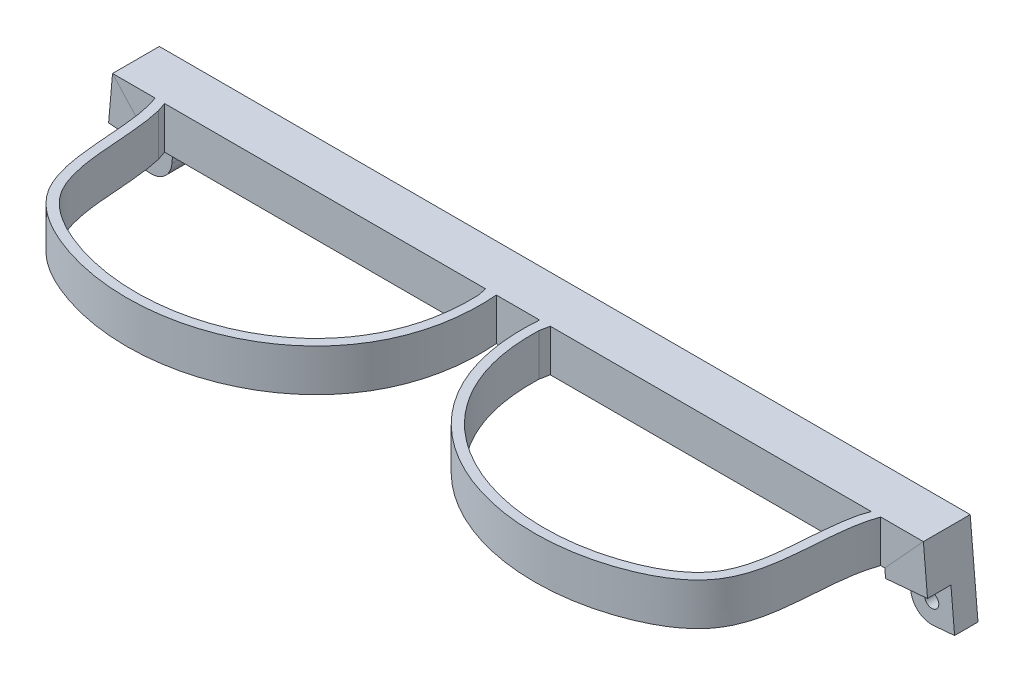
SolidWorks part; units mm, degrees
ref_plane "前视基准面" through (0, 0, 0) normal (0, 0, 1) x (1, 0, 0)
ref_plane "上视基准面" through (0, 0, 0) normal (0, 1, 0) x (1, 0, 0)
ref_plane "右视基准面" through (0, 0, 0) normal (1, 0, 0) x (0, 0, -1)
sketch "草图1" plane through (0, 0, 0) normal (0, 1, 0) x (1, 0, 0)
  line L0 (-85, 29.8187) -> (85, 29.8187)
  line L1 (85, 29.8187) -> (85, -30.1813)
  line L2 (85, -30.1813) -> (-85, -30.1813)
  line L3 (-85, -30.1813) -> (-85, 29.8187)
  line L4 (-77.5, 21.6616) -> (77.5, 21.6616)
  line L5 (-77.5, 21.6616) -> (-77.5, 11.6616)
  line L6 (-77.5, 11.6616) -> (-4.6224, 11.6616)
  line L8 (-74.8263, 9.6616) -> (-6.5113, 9.6616) construction
  line L10 (-4.6224, 11.6616) -> (4.6224, 11.6616)
  line L11 (0, 29.8187) -> (0, -30.1813) construction
  line L12 (77.5, 11.6616) -> (4.6224, 11.6616)
  line L13 (77.5, 21.6616) -> (77.5, 11.6616)
  spline S0 degree 3 poles (-77.5, 11.6616) (-74.4077, 3.1869) (-78.1308, -15.9273) (-40.2589, -37.426) (-2.1163, -20.689) (-4.6224, 11.6616) knots 0 0 0 0 0.246122 0.369792 1 1 1 1
  spline S1 degree 1 poles (-74.8263, 9.6616) (-6.5113, 9.6616) knots 0 0 1 1 construction
  spline S2 degree 3 poles (-74.8263, 9.6616) (-74.5371, 8.4402) (-74.1186, 5.9785) (-73.6218, 0.8691) (-73.2546, -5.557) (-72.241, -11.3706) (-70.6014, -15.2078) (-68.2701, -18.4305) (-63.7315, -21.7629) (-56.8543, -24.5334) (-49.7226, -26.1197) (-40.0582, -26.6566) (-30.6361, -24.878) (-22.3142, -20.9083) (-16.8289, -16.8747) (-12.2912, -11.8166) (-9.4499, -6.76) (-7.8343, -2.2025) (-6.9771, 1.4731) (-6.5812, 4.7599) (-6.4697, 7.5102) (-6.4856, 8.9503) (-6.5113, 9.6616) knots 0.022831 0.022831 0.022831 0.022831 0.052972 0.083113 0.143395 0.203676 0.233817 0.263958 0.324239 0.384521 0.444802 0.505084 0.625647 0.685929 0.74621 0.806492 0.866773 0.896914 0.927055 0.957196 0.972266 0.987337 0.987337 0.987337 0.987337
  spline S3 degree 1 poles (-74.8263, 9.6616) (-75.4985, 11.6616) knots 0 0 1 1
  spline S4 degree 1 poles (-6.5113, 9.6616) (-6.9074, 11.6616) knots 0 0 1 1
  spline S5 degree 1 poles (74.8263, 9.6616) (75.4985, 11.6616) knots 0 0 1 1
  spline S6 degree 1 poles (6.5113, 9.6616) (6.9074, 11.6616) knots 0 0 1 1
  spline S7 degree 3 poles (74.8263, 9.6616) (74.5371, 8.4402) (74.1186, 5.9785) (73.6218, 0.8691) (73.2546, -5.557) (72.241, -11.3706) (70.6014, -15.2078) (68.2701, -18.4305) (63.7315, -21.7629) (56.8543, -24.5334) (49.7226, -26.1197) (40.0582, -26.6566) (30.6361, -24.878) (22.3142, -20.9083) (16.8289, -16.8747) (12.2912, -11.8166) (9.4499, -6.76) (7.8343, -2.2025) (6.9771, 1.4731) (6.5812, 4.7599) (6.4697, 7.5102) (6.4856, 8.9503) (6.5113, 9.6616) knots 0.022831 0.022831 0.022831 0.022831 0.052972 0.083113 0.143395 0.203676 0.233817 0.263958 0.324239 0.384521 0.444802 0.505084 0.625647 0.685929 0.74621 0.806492 0.866773 0.896914 0.927055 0.957196 0.972266 0.987337 0.987337 0.987337 0.987337
  spline S8 degree 3 poles (77.5, 11.6616) (74.4077, 3.1869) (78.1308, -15.9273) (40.2589, -37.426) (2.1163, -20.689) (4.6224, 11.6616) knots 0 0 0 0 0.246122 0.369792 1 1 1 1
  point P3 (0, 29.8187)
  point P25 (0, 11.6616)
  point P31 (0, 21.6616)
  dimension "D1" = 60
  dimension "D2" = 170
  dimension "D3" = 10
  dimension "D4" = 77.5
  dimension "D5" = 2
extrude "frame_前端" add sketch "草图1" along normal blind 9 contours L13 L4 L5 L6 L10 L12 | S8 L12 S5 S7 S6 | S4 S2 S3 L6 S0 region at (0, 0, -16.6616) region at (-76.4992, 0, -10.8291) region at (42.3457, 0, 27.4934)
sketch "左镜腿扫描截面草图" plane through (77.5, 0, 0) normal (1, 0, 0) x (0, 0, -1)
  line L0 (11.6616, 9) -> (11.6616, 0)
  line L1 (11.6616, 9) -> (11.6616, 0) construction
  line L2 (11.6616, 0) -> (21.6616, 0)
  line L3 (21.6616, 0) -> (21.6616, 9)
  line L4 (21.6616, 9) -> (11.6616, 9)
  line L5 (11.6616, 9) -> (21.6616, 0) construction
  line L6 (11.6616, 0) -> (21.6616, 9) construction
  point P7 (16.6616, 4.5)
ref_plane "左侧镜腿轨迹基准面" through (0, 0, -16.6616) normal (0, 0, -1) x (-1, 0, 0)
sketch "左侧镜腿轨迹草图" plane through (0, 0, -16.6616) normal (0, 0, -1) x (-1, 0, 0)
  line L0 (-77.5, 4.5) -> (-82.5, 4.5)
  line L1 (-77.5, 0) -> (-77.5, 9) construction
  line L2 (-82.5, 4.5) -> (-83.8073, -10.4429)
  dimension "D1" = 5
  dimension "D2" = 15
  dimension "D3" = 95
sweep "左侧connection生成" add profiles "左镜腿扫描截面草图" path "左侧镜腿轨迹草图"
sketch "草图20" plane through (0, 0, -21.6616) normal (0, 0, -1) x (-1, 0, 0)
  line L8 (-79.3245, -10.8351) -> (-83.8073, -10.4429)
  line L9 (-79.3245, -10.8351) -> (-88.2902, -10.0507) construction
  line L10 (-78.3765, 0) -> (-79.3245, -10.8351) construction
  line L11 (-78.9323, -6.3522) -> (-79.3245, -10.8351)
  arc A1 (-83.8073, -10.4429) -> (-78.9323, -6.3522) centre (-83.4151, -5.96) ccw
  point P13 (-79.3245, -10.8351)
  dimension "D1" = 4.5
extrude "左侧connection圆角化" cut sketch "草图20" against normal through all
sketch "孔左" plane through (0, 0, -21.6616) normal (0, 0, -1) x (-1, 0, 0)
  line L4 (-78.9323, -6.3522) -> (-78.3765, 0)
  line L5 (-78.3765, 0) -> (-86.6235, 9)
  line L6 (-86.6235, 9) -> (-88.2902, -10.0507)
  line L7 (-88.2902, -10.0507) -> (-83.8073, -10.4429)
  line L8 (-78.9323, -6.3522) -> (-78.3765, 0)
  line L9 (-78.3765, 0) -> (-86.6235, 9)
  line L10 (-86.6235, 9) -> (-88.2902, -10.0507)
  line L11 (-88.2902, -10.0507) -> (-83.8073, -10.4429)
  arc A1 (-83.8073, -10.4429) -> (-78.9323, -6.3522) centre (-83.4151, -5.96) ccw
  circle A3 centre (-83.4151, -5.96) radius 1.5
  arc A4 (-83.8073, -10.4429) -> (-78.9323, -6.3522) centre (-83.4151, -5.96) ccw
  dimension "D2" = 3
  dimension "D1" = 0
ref_plane "右侧镜腿轨迹基准面" through (0, 0, -16.6616) normal (0, 0, -1) x (-1, 0, 0)
sketch "草图22" plane through (0, 0, -16.6616) normal (0, 0, -1) x (-1, 0, 0)
  line L0 (77.5, 4.5) -> (82.5, 4.5)
  line L1 (77.5, 9) -> (77.5, 0) construction
  line L2 (82.5, 4.5) -> (83.8073, -10.4429)
  dimension "D1" = 5
  dimension "D2" = 15
  dimension "D3" = 95
sketch "草图23" plane through (-77.5, 0, 0) normal (-1, 0, 0) x (0, 0, 1)
  line L2 (-21.6616, 0) -> (-11.6616, 0)
  line L3 (-11.6616, 0) -> (-11.6616, 9)
  line L6 (-21.6616, 9) -> (-21.6616, 0)
  line L7 (-21.6616, 0) -> (-21.6616, 9) construction
  line L8 (-21.6616, 9) -> (-11.6616, 9) construction
  line L9 (-21.6616, 9) -> (-11.6616, 9)
sweep "右侧connection生成" add profiles "草图23" path "草图22"
sketch "草图24" plane through (0, 0, -21.6616) normal (0, 0, -1) x (-1, 0, 0)
  line L2 (88.2902, -10.0507) -> (79.3245, -10.8351) construction
  line L3 (79.3245, -10.8351) -> (83.8073, -10.4429)
  line L4 (79.3245, -10.8351) -> (78.9323, -6.3522)
  line L5 (78.3765, 0) -> (79.3245, -10.8351) construction
  circle A1 centre (83.4151, -5.96) radius 1.5
  arc A2 (78.9323, -6.3522) -> (83.8073, -10.4429) centre (83.4151, -5.96) ccw
  point P11 (83.4151, -6.0699)
  dimension "D3" = 3
  dimension "D1" = 4.5
extrude "右侧孔and_connection圆角化" cut sketch "草图24" against normal through all
ref_plane "线槽口草图基准面" through (0, 0, 0) normal (1, 0, 0) x (0, 0, -1)
sketch "草图25" plane through (0, 0, 0) normal (1, 0, 0) x (0, 0, -1)
  line L6 (21.6616, 9) -> (21.6616, -10.0507) construction
  line L9 (11.6616, 9) -> (21.6616, 0) construction
  line L10 (11.6616, 0) -> (21.6616, 9) construction
  line L11 (13.6616, 0) -> (13.6616, 7.2)
  line L12 (13.6616, 7.2) -> (19.6616, 7.2)
  line L13 (19.6616, 7.2) -> (19.6616, 0)
  line L14 (13.6616, 0) -> (19.6616, 0)
  dimension "D1" = 2
  dimension "D2" = 2
extrude "挖槽右" cut sketch "草图25" against normal blind 77.5
extrude "挖槽左" cut sketch "草图25<2>" along normal blind 77.5
sketch "草图25<2>" plane through (0, 0, 0) normal (1, 0, 0) x (0, 0, -1) same geometry as "草图25"
sketch "草图26" plane through (0, 0, -21.6616) normal (0, 0, -1) x (-1, 0, 0)
  line L6 (-88.2902, -10.0507) -> (-87.5058, -1.085)
  line L7 (-86.6235, 9) -> (-88.2902, -10.0507) construction
  line L8 (-87.5058, -1.085) -> (-78.5401, -1.8694)
  line L9 (-78.9323, -6.3522) -> (-78.3765, 0) construction
  line L10 (-78.5401, -1.8694) -> (-78.9323, -6.3522)
  line L11 (-88.2902, -10.0507) -> (-83.8073, -10.4429)
  line L12 (-88.2902, -10.0507) -> (-83.8073, -10.4429) construction
  arc A1 (-83.8073, -10.4429) -> (-78.9323, -6.3522) centre (-83.4151, -5.96) ccw
  dimension "D2" = 4.5
  dimension "D1" = 9
  dimension "D3" = 4.5
extrude "挖孔左" cut sketch "孔左" against normal through all contours A3
ref_plane "基准面1" through (0, 0, -16.6616) normal (0, 0, -1) x (-1, 0, 0)
sketch "草图27" plane through (0, 0, -16.6616) normal (0, 0, -1) x (-1, 0, 0)
  line L0 (-87.5058, -1.085) -> (-78.5401, -1.8694)
  line L1 (-78.5401, -1.8694) -> (-78.9323, -6.3522)
  line L2 (-87.5058, -1.085) -> (-88.2902, -10.0507)
  line L3 (-88.2902, -10.0507) -> (-83.8073, -10.4429)
  arc A0 (-83.8073, -10.4429) -> (-78.9323, -6.3522) centre (-83.4151, -5.96) ccw
extrude "左侧connection口" cut sketch "草图27" against normal blind 5
ref_plane "基准面2" through (0, 0, -16.6616) normal (0, 0, -1) x (-1, 0, 0)
sketch "草图30" plane through (0, 0, -16.6616) normal (0, 0, -1) x (-1, 0, 0)
  line L0 (88.2902, -10.0507) -> (83.8073, -10.4429)
  line L1 (88.2902, -10.0507) -> (87.4599, -0.5607)
  line L2 (86.6235, 9) -> (88.2902, -10.0507) construction
  line L3 (87.4599, -0.5607) -> (78.4942, -1.3451)
  line L4 (78.3765, 0) -> (78.9323, -6.3522) construction
  line L5 (78.4942, -1.3451) -> (78.9323, -6.3522)
  arc A0 (78.9323, -6.3522) -> (83.8073, -10.4429) centre (83.4151, -5.96) ccw
extrude "切除-拉伸4" cut sketch "草图30" against normal blind 5
